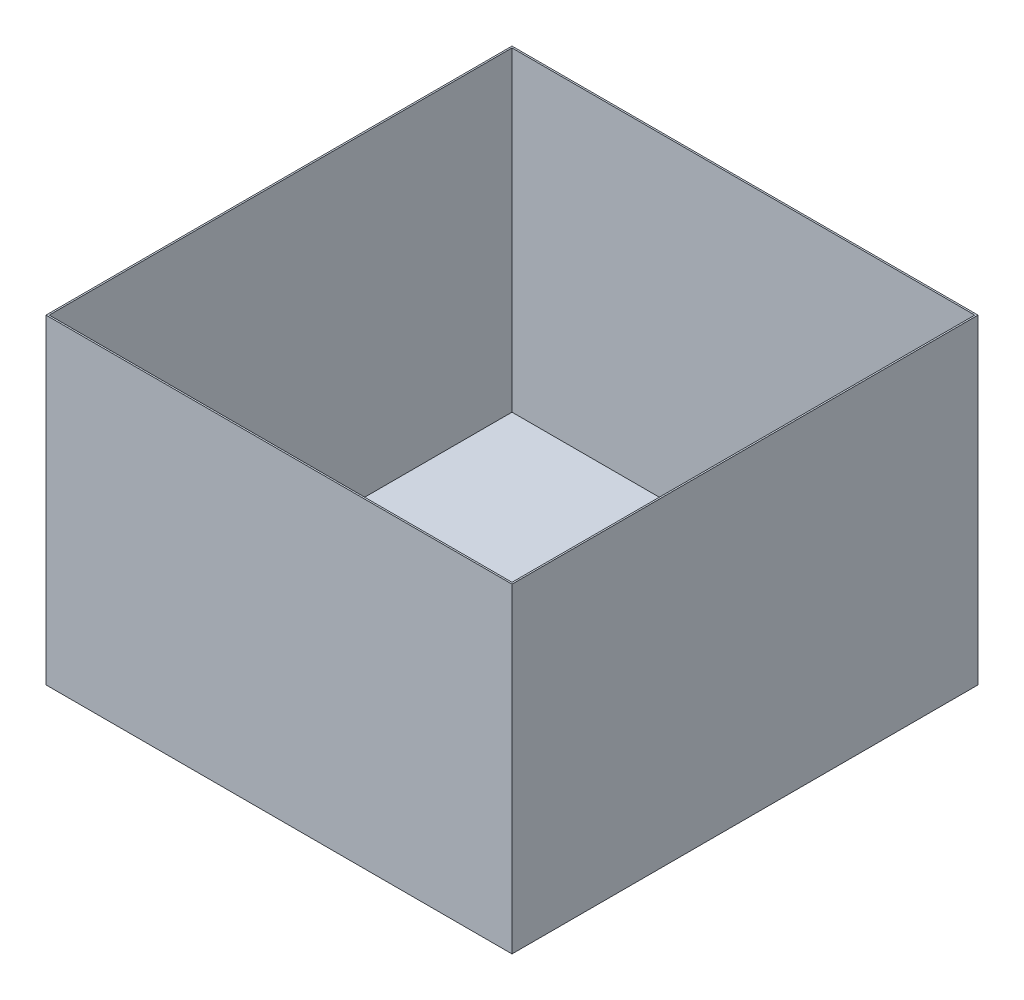
SolidWorks part; units mm, degrees
ref_plane "Front Plane" through (0, 0, 0) normal (0, 0, 1) x (1, 0, 0)
ref_plane "Top Plane" through (0, 0, 0) normal (0, 1, 0) x (1, 0, 0)
ref_plane "Right Plane" through (0, 0, 0) normal (1, 0, 0) x (0, 0, -1)
sketch "Sketch1" plane through (0, 0, 0) normal (0, 1, 0) x (1, 0, 0)
  line L1 (-461.9625, -461.9625) -> (461.9625, -461.9625)
  line L2 (-461.9625, -461.9625) -> (-461.9625, 461.9625)
  line L3 (-461.9625, 461.9625) -> (461.9625, 461.9625)
  line L4 (461.9625, -461.9625) -> (461.9625, 461.9625)
  line L5 (-461.9625, -461.9625) -> (461.9625, 461.9625) construction
  line L6 (-461.9625, 461.9625) -> (461.9625, -461.9625) construction
  line L7 (-458.7875, -458.7875) -> (458.7875, -458.7875)
  line L8 (-458.7875, -458.7875) -> (-458.7875, 458.7875)
  line L9 (-458.7875, 458.7875) -> (458.7875, 458.7875)
  line L10 (458.7875, -458.7875) -> (458.7875, 458.7875)
  line L11 (-458.7875, -458.7875) -> (458.7875, 458.7875) construction
  line L12 (-458.7875, 458.7875) -> (458.7875, -458.7875) construction
  point P0 (0, 0)
  point P6 (0, 0)
  dimension "D1" = 923.925
  dimension "D2" = 923.925
  dimension "D3" = 3.175
extrude "Boss-Extrude1" add sketch "Sketch1" along normal blind 635
extrude "Boss-Extrude2" add sketch "Sketch1<2>" along normal blind 9.525 contours L7 L10 L9 L8 region at (0, 0, 0)
sketch "Sketch1<2>" plane through (0, 0, 0) normal (0, 1, 0) x (1, 0, 0) same geometry as "Sketch1"
